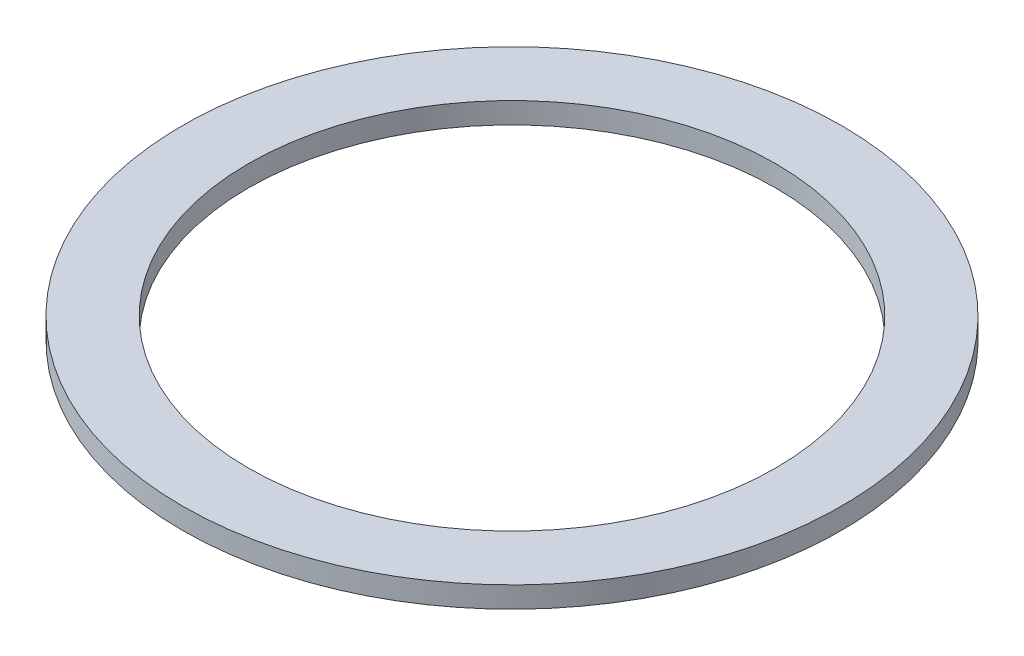
SolidWorks part; units mm, degrees
ref_plane "Front Plane" through (0, 0, 0) normal (0, 0, 1) x (1, 0, 0)
ref_plane "Top Plane" through (0, 0, 0) normal (0, 1, 0) x (1, 0, 0)
ref_plane "Right Plane" through (0, 0, 0) normal (1, 0, 0) x (0, 0, -1)
sketch "Sketch1" plane through (0, 0, 0) normal (0, 1, 0) x (1, 0, 0)
  circle A0 centre (0, 0) radius 62.5
  dimension "FLANGE_OD" = 125
extrude "Boss-Extrude1" add sketch "Sketch1" along normal blind 4
sketch "Sketch2" plane through (0, 0, 0) normal (0, 1, 0) x (1, 0, 0)
  circle A0 centre (0, 0) radius 50
  dimension "BORE_D" = 100
extrude "Cut-Extrude1" cut sketch "Sketch2" along normal through all
sketch "Sketch3" plane through (0, 4, 0) normal (0, 1, 0) x (1, 0, 0)
  circle A0 centre (0, 0) radius 28.6933 construction
  circle A1 centre (-28.6933, 0) radius 1.813
  dimension "BOLT_D" = 3.6261
  dimension "BOLT_PCD" = 57.3866
extrude "Cut-Extrude2" cut sketch "Sketch3" against normal blind 2.8699 rebuild error yes
pattern_circular "CirPattern1" count 8 over 360 rebuild error yes
